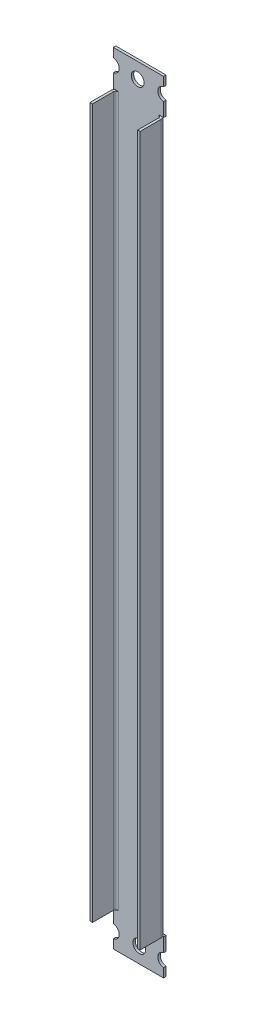
SolidWorks part; units mm, degrees
note: The reader was unsure of these and kept them because the rebuilt part matched: flange length of "Brida de arista1".
ref_plane "Alzado" through (0, 0, 0) normal (0, 0, 1) x (1, 0, 0)
ref_plane "Planta" through (0, 0, 0) normal (0, 1, 0) x (1, 0, 0)
ref_plane "Vista lateral" through (0, 0, 0) normal (1, 0, 0) x (0, 0, -1)
sketch "Croquis1" plane through (0, 0, 0) normal (0, 0, 1) x (1, 0, 0)
  line L0 (0, 231.775) -> (0, -231.775) construction
  line L1 (-15.494, -241.3) -> (15.494, -241.3)
  line L2 (-15.494, -241.3) -> (-15.494, 241.3)
  line L3 (-15.494, 241.3) -> (15.494, 241.3)
  line L4 (15.494, -241.3) -> (15.494, 241.3)
  line L5 (-15.494, -241.3) -> (15.494, 241.3) construction
  line L6 (-15.494, 241.3) -> (15.494, -241.3) construction
  circle A0 centre (-0.508, 231.775) radius 3.9624
  circle A1 centre (0.508, -231.775) radius 3.9624
  point P0 (0, 0)
  point P12 (0, 0)
  dimension "D6" = 7.9248
  dimension "D1" = 482.6
  dimension "D2" = 30.988
  dimension "D3" = 463.55
  dimension "D4" = 16.002
  dimension "D5" = 16.002
base flange "Brida base1" sketch "Croquis1" thickness 1.524 reverse thickness direction no parameters "D1"=1.524
edge flange "Brida de arista1" sketch "Croquis12" flange profiles "Croquis12", "Croquis14" flange angle 90 flange length 16.002 flange position material inside bend radius 1.524 thickness 1.524 relief rectangular parameters "D6"=10, "D8"=1
sketch "Croquis12" plane through (15.494, 0, 0) normal (1, 0, 0) x (0, 1, 0)
  line L2 (-219.075, 0) -> (-219.075, 14.478)
  line L3 (-219.075, 14.478) -> (219.075, 14.478)
  line L4 (219.075, 14.478) -> (219.075, 0)
  line L7 (-241.3, 0) -> (241.3, 0) construction
  line L8 (-219.075, 0) -> (219.075, 0)
  line L9 (-241.3, 0) -> (-219.075, 0) construction
  line L10 (219.075, 0) -> (241.3, 0) construction
  dimension "D1" = 438.15
sketch "Croquis14" plane through (-15.494, 0, 0) normal (-1, 0, 0) x (0, -1, 0)
  line L0 (-241.3, 0) -> (241.3, 0) construction
  line L1 (-219.075, 0) -> (219.075, 0)
  line L2 (-219.075, 0) -> (-219.075, 14.478)
  line L3 (-219.075, 14.478) -> (219.075, 14.478)
  line L4 (219.075, 14.478) -> (219.075, 0)
bend "Pliegue de arista1" bend radius 1.524 bend angle 90 parameters "D5"=1
bend "Pliegue de arista2" bend radius 1.524 bend angle 90 parameters "D5"=3
sketch "Croquis15" plane through (0, 0, 0) normal (0, 0, 1) x (1, 0, 0)
  line L0 (0, 241.3) -> (0, -241.3) construction
  line L6 (15.494, 241.3) -> (-15.494, 241.3) construction
  line L23 (-15.494, -241.3) -> (15.494, -241.3) construction
  line L24 (-15.494, 241.3) -> (-15.494, 219.2274) construction
  circle A4 centre (-15.9004, 231.775) radius 3.9624
  circle A5 centre (-15.9004, -231.775) radius 3.9624
  circle A6 centre (15.9004, -231.775) radius 3.9624
  circle A7 centre (15.9004, 231.775) radius 3.9624
  dimension "D3" = 9.525
  dimension "D4" = 7.9248
  dimension "D1" = 0.4064
  dimension "D2" = 9.525
extrude "Cortar-Extruir1" cut sketch "Croquis15" against normal through all
sketch "Líneas de pliegue1" [suppressed] plane through (0, 0, 0) normal (0, 1, 0) x (1, 0, 0)
sketch "Cuadro delimitador1" [suppressed] plane through (0, 0, 0) normal (0, 1, 0) x (1, 0, 0)
sheet metal parameters "Chapa metálica1" thickness 1.524 parameters "D1"=6.35
flat pattern "Chapa desplegada1" [suppressed]
sketch "Líneas de pliegue2" plane through (0, 0, 0) normal (0, 1, 0) x (1, 0, 0)
sketch3d "Cuadro delimitador2" [suppressed]
  line L0 (-47.244, 241.3, 0) -> (-47.244, -241.3, 0) construction
  line L1 (47.244, 241.3, 0) -> (47.244, -241.3, 0) construction
  line L2 (-47.244, 241.3, 0) -> (47.244, 241.3, 0) construction
  line L3 (-47.244, -241.3, 0) -> (47.244, -241.3, 0) construction
sheet metal parameters "Chapa metálica2" thickness 1.524 parameters "D1"=6.35
flat pattern "Chapa desplegada1" [suppressed]
sketch "Líneas de pliegue2" plane through (0, 0, 0) normal (0, 0, 1) x (1, 0, 0)
  line L0 (204.7175, -219.075) -> (204.7175, 219.075) construction
  line L1 (204.7175, -219.075) -> (204.7175, 219.075) construction
  line L2 (-204.7175, 219.075) -> (-204.7175, -219.075) construction
  line L3 (-204.7175, 219.075) -> (-204.7175, -219.075) construction
sketch3d "Cuadro delimitador2" [suppressed]
  line L0 (219.443, 241.3, 0) -> (219.443, -241.3, 0) construction
  line L1 (-219.443, 241.3, 0) -> (-219.443, -241.3, 0) construction
  line L2 (219.443, 241.3, 0) -> (-219.443, 241.3, 0) construction
  line L3 (219.443, -241.3, 0) -> (-219.443, -241.3, 0) construction
bend of the flat pattern "Aplanar-<Pliegue de arista1>1"
bend of the flat pattern "Aplanar-<Pliegue de arista2>1"
sheet metal parameters "Chapa metálica3" thickness 1.524 parameters "D1"=6.35
flat pattern "Chapa desplegada1"
sketch "Líneas de pliegue2" plane through (0, 0, 0) normal (0, 0, 1) x (1, 0, 0)
  line L0 (204.7414, -219.075) -> (204.7414, 219.075) construction
  line L1 (204.7414, -219.075) -> (204.7414, 219.075) construction
  line L2 (-204.7414, 219.075) -> (-204.7414, -219.075) construction
  line L3 (-204.7414, 219.075) -> (-204.7414, -219.075) construction
sketch3d "Cuadro delimitador2" [suppressed]
  line L0 (219.4908, 241.3, 0) -> (219.4908, -241.3, 0) construction
  line L1 (-219.4908, 241.3, 0) -> (-219.4908, -241.3, 0) construction
  line L2 (219.4908, 241.3, 0) -> (-219.4908, 241.3, 0) construction
  line L3 (219.4908, -241.3, 0) -> (-219.4908, -241.3, 0) construction
sheet metal parameters "Chapa metálica5" thickness 1.524 parameters "D1"=6.35
flat pattern "Chapa desplegada1"
sketch "Líneas de pliegue2" plane through (0, 0, 0) normal (0, 0, 1) x (1, 0, 0)
  line L0 (-14.2175, 219.075) -> (-14.2175, -219.075) construction
  line L1 (14.2175, -219.075) -> (14.2175, 219.075) construction
  line L2 (-14.2175, 219.075) -> (-14.2175, -219.075) construction
  line L3 (14.2175, -219.075) -> (14.2175, 219.075) construction
sketch3d "Cuadro delimitador2" [suppressed]
  line L0 (28.943, 241.3, 0) -> (28.943, -241.3, 0) construction
  line L1 (-28.943, 241.3, 0) -> (-28.943, -241.3, 0) construction
  line L2 (28.943, 241.3, 0) -> (-28.943, 241.3, 0) construction
  line L3 (28.943, -241.3, 0) -> (-28.943, -241.3, 0) construction
bend of the flat pattern "Aplanar-<Pliegue de arista1>3"
bend of the flat pattern "Aplanar-<Pliegue de arista2>3"
sheet metal parameters "Chapa metálica6" thickness 1.524 parameters "D1"=6.35
flat pattern "Chapa desplegada6"
sketch "Líneas de pliegue4" plane through (-205.994, 0, 0) normal (-1, 0, 0) x (0, 0, 1)
  line L0 (-0.2475, 219.075) -> (-0.2475, -219.075) construction
  line L1 (-0.2475, 219.075) -> (-0.2475, -219.075) construction
sketch3d "Cuadro delimitador4" [suppressed]
  line L0 (-2.019, 219.075, 0) -> (-2.019, -219.075, 0) construction
  line L1 (14.478, 219.075, 0) -> (14.478, -219.075, 0) construction
  line L2 (-2.019, 219.075, 0) -> (14.478, 219.075, 0) construction
  line L3 (-2.019, -219.075, 0) -> (14.478, -219.075, 0) construction
sheet metal parameters "Chapa metálica7" thickness 1.524 parameters "D1"=6.35
flat pattern "Chapa desplegada7"
sketch "Líneas de pliegue5" plane through (0, 0, 0) normal (0, 1, 0) x (1, 0, 0)
sketch "Cuadro delimitador5" [suppressed] plane through (0, 0, 0) normal (0, 1, 0) x (1, 0, 0)
equation "\"A\"= 1.22pulgadas"
equation "\"B\"= 0.63pulgadas"
equation "\"D2@Croquis1\"=\"A\""
equation "\"D4@Croquis1\"=\"B\""
equation "\"D5@Croquis1\"=\"B\""
